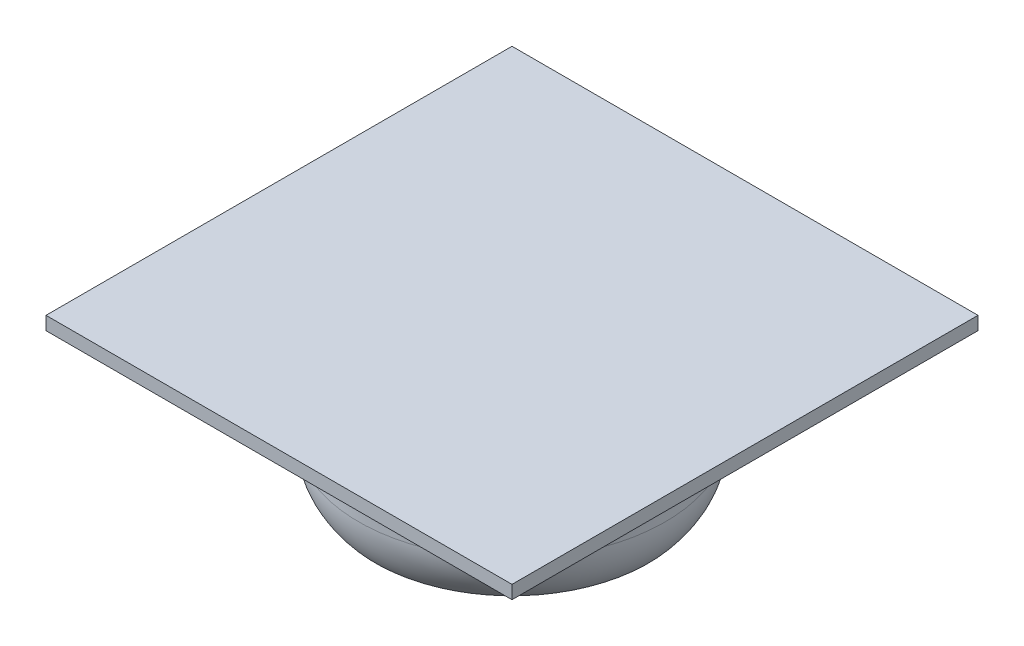
SolidWorks part; units mm, degrees
ref_plane "Front Plane" through (0, 0, 0) normal (0, 0, 1) x (1, 0, 0)
ref_plane "Top Plane" through (0, 0, 0) normal (0, 1, 0) x (1, 0, 0)
ref_plane "Right Plane" through (0, 0, 0) normal (1, 0, 0) x (0, 0, -1)
sketch "Sketch1" plane through (0, 0, 0) normal (0, 1, 0) x (1, 0, 0)
  line L1 (0, 0) -> (35, 0)
  line L2 (0, 0) -> (0, 35)
  line L3 (0, 35) -> (35, 35)
  line L4 (35, 0) -> (35, 35)
  dimension "D1" = 35
extrude "Boss-Extrude1" add sketch "Sketch1" along normal blind 1
sketch "Sketch3" plane through (0, 0, 0) normal (0, -1, 0) x (1, 0, 0)
  line L0 (17.5, 0) -> (17.5, -35) construction
  line L1 (0, 0) -> (35, 0) construction
  line L2 (35, -35) -> (0, -35) construction
  line L3 (0, -17.5) -> (35, -17.5) construction
  line L4 (0, -35) -> (0, 0) construction
  line L5 (35, 0) -> (35, -35) construction
  circle A0 centre (17.5, -17.5) radius 11.5
  circle A1 centre (17.5, -17.5) radius 10.25
  dimension "D1" = 20.5
  dimension "D2" = 23
extrude "Boss-Extrude3" add sketch "Sketch3" along normal blind 10
fillet "Fillet1" radius 5 1 edges at (17.5, -10, -29)
